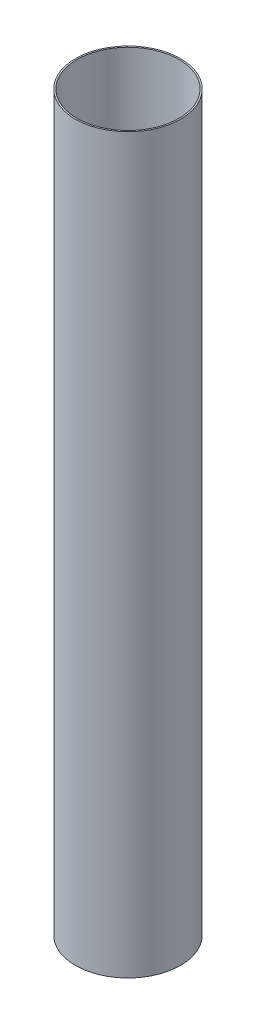
SolidWorks part; units mm, degrees
material "E-Glass Fiber"
ref_plane "Front Plane" through (0, 0, 0) normal (0, 0, 1) x (1, 0, 0)
ref_plane "Top Plane" through (0, 0, 0) normal (0, 1, 0) x (1, 0, 0)
ref_plane "Right Plane" through (0, 0, 0) normal (1, 0, 0) x (0, 0, -1)
sketch "Motor Mount Profile Sketch" plane through (0, 0, 0) normal (0, 1, 0) x (1, 0, 0)
  circle A0 centre (0, 0) radius 50.9778
  circle A1 centre (0, 0) radius 49.53
  dimension "D1" = 101.9556
  dimension "D2" = 99.06
extrude "Motor Mount Body" add sketch "Motor Mount Profile Sketch" along normal blind 711.2
equation "\"Length\"= 28"
equation "\"Outer Diameter\"= 4.014"
equation "\"Inner Diameter\"= 3.9"
equation "\"Wall Thickness\"= 0.062"
equation "\"D1@Motor Mount Profile Sketch\" = \"Outer Diameter\""
equation "\"D2@Motor Mount Profile Sketch\" = \"Inner Diameter\""
equation "\"D1@Motor Mount Body\" = \"Length\""
